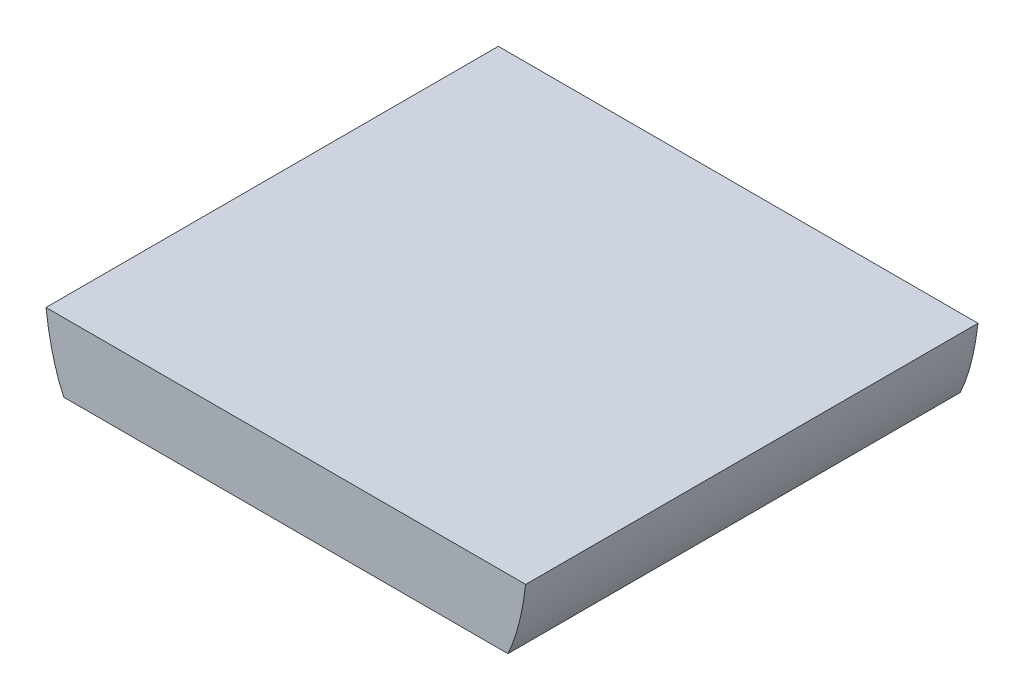
SolidWorks part; units mm, degrees
ref_plane "Front Plane" through (0, 0, 0) normal (0, 0, 1) x (1, 0, 0)
ref_plane "Top Plane" through (0, 0, 0) normal (0, 1, 0) x (1, 0, 0)
ref_plane "Right Plane" through (0, 0, 0) normal (1, 0, 0) x (0, 0, -1)
sketch "Sketch1" plane through (0, 0, 0) normal (0, 0, 1) x (1, 0, 0)
  line L0 (0, 0) -> (0, 222.758) construction
  line L2 (-350.1769, 222.758) -> (0, 222.758)
  line L3 (0, 222.758) -> (350.1769, 222.758)
  conic Q0 (350.1769, 222.758) -> (0, 0) control (323.6021, 0) rho 0.570465
  conic Q1 (-350.1769, 222.758) -> (0, 0) control (-323.6021, 0) rho 0.570465
extrude "Boss-Extrude1" add sketch "Sketch1" against normal blind 330.2 and the other way blind 330.2 contours Q0 Q1 L2 L3
sketch "Sketch6" plane through (0, 0, 0) normal (1, 0, 0) x (0, 0, -1)
  line L0 (0, 0) -> (402.7895, 12.7)
  line L1 (0, 0) -> (0, 317.8845) construction
  line L2 (0, 0) -> (-402.7895, 12.7)
  dimension "D1" = 12.7
ref_plane "Plane1" through (304.8, 0, 0) normal (1, 0, 0) x (0, 0, -1)
ref_plane "Plane2" [suppressed] through (0, 0, 401.32) normal (0, 0, 1) x (1, 0, 0)
sketch "Sketch29" plane through (0, 0, 0) normal (1, 0, 0) x (0, 0, -1)
  line L0 (0, 7.9367) -> (74.9675, 7.9367)
  line L1 (74.9675, 7.9367) -> (308.7791, 142.4931)
  line L3 (308.7791, 142.4931) -> (642.4614, 142.4931)
  point P6 (0, -63.5)
sweep "Engine Line" [suppressed] add path "Sketch29" circular profile diameter 12.7 parameters "D3"=12.7
sketch "Sketch42" plane through (0, 0, 0) normal (0, 0, 1) x (1, 0, 0)
  circle A0 centre (0, 6.35) radius 6.35
extrude "Boss-Extrude2" [suppressed] add sketch "Sketch42" against normal blind 635
sketch "Sketch43" plane through (0, 0, -330.2) normal (0, 0, -1) x (-1, 0, 0)
  circle A0 centre (0, 209.4482) radius 6.35
extrude "Boss-Extrude3" [suppressed] add sketch "Sketch43" along normal blind 142.748
ref_plane "Plane4" through (0, 0, 381) normal (0, 0, 1) x (1, 0, 0)
sketch "Sketch41" plane through (0, 0, 381) normal (0, 0, 1) x (1, 0, 0)
  line L0 (-0.3885, -71.0751) -> (-0.3885, 316.4102) construction
  conic Q0 (-0.3885, -71.0751) -> (301.9685, 246.7379) control (301.9685, -71.1416) rho 0.504796
  conic Q1 (-0.3885, -71.0751) -> (-302.7456, 246.7379) control (-302.7456, -71.1416) rho 0.504796
ref_plane "Plane5" through (350.1769, 0, 0) normal (1, 0, 0) x (0, 0, -1)
sketch "Sketch44" plane through (350.1769, 0, 0) normal (1, 0, 0) x (0, 0, -1)
  circle A0 centre (-360.0842, 200.1725) radius 12.7
sketch "Sketch45" plane through (0, 0, 0) normal (0, 0, 1) x (1, 0, 0)
  line L0 (-363.6888, 122.174) -> (403.1456, 122.174)
  line L1 (-350.1769, 222.758) -> (350.1769, 222.758) construction
  dimension "D1" = 100.584
split "Split1" trim tools "Sketch45" bodies to split 103 resulting bodies 127
